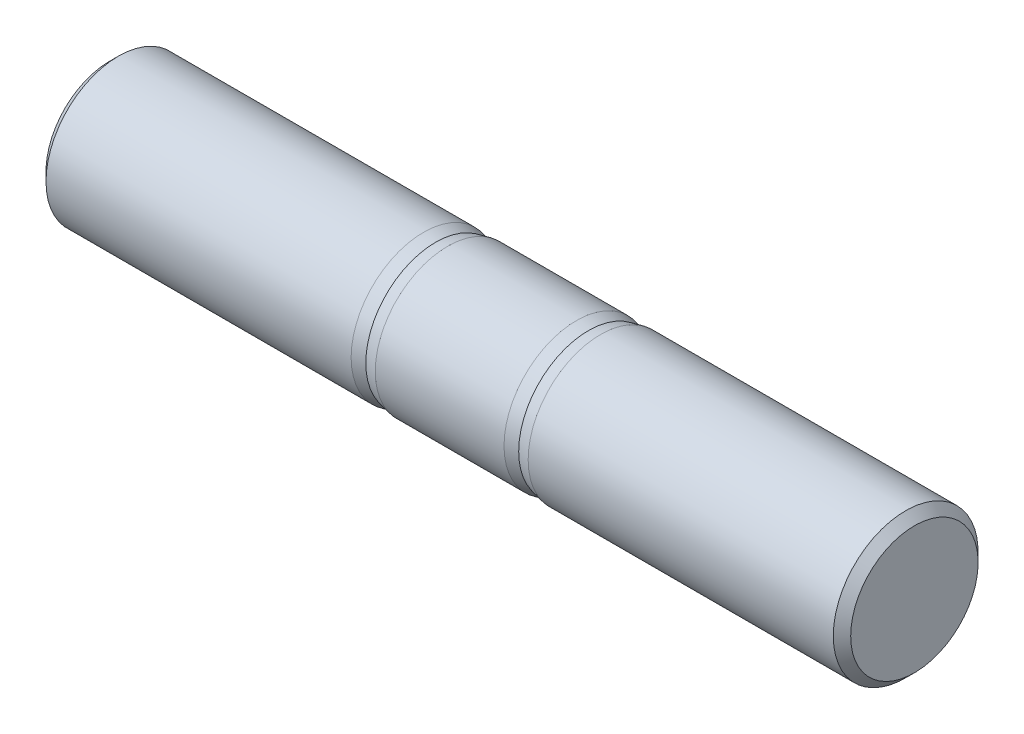
SolidWorks part; units mm, degrees
ref_plane "Front" through (0, 0, 0) normal (0, 0, 1) x (1, 0, 0)
ref_plane "Top" through (0, 0, 0) normal (0, 1, 0) x (1, 0, 0)
ref_plane "Right" through (0, 0, 0) normal (1, 0, 0) x (0, 0, -1)
sketch "Sketch1" plane through (0, 0, 0) normal (0, 0, 1) x (1, 0, 0)
  line L0 (-1.3108, 0) -> (30.3862, 0) construction
  line L1 (0, 0) -> (0, 18)
  line L2 (0, 18) -> (78, 18)
  line L3 (78, 18) -> (84, 16.701)
  line L4 (84, 16.701) -> (116, 16.701)
  line L5 (116, 16.701) -> (122, 18)
  line L6 (122, 18) -> (200, 18)
  line L7 (200, 18) -> (200, 0)
  line L8 (200, 0) -> (0, 0)
  dimension "D2" = 6
  dimension "D1" = 78
  dimension "l" = 200
  dimension "b" = 78
revolve "Base" add sketch "Sketch1" angle 360 about L0
cosmetic thread "ThreadCosmetic1" [suppressed] parameters "D1"=78, "D2"=31.67
cosmetic thread "ThreadCosmetic2" [suppressed] parameters "b"=78, "D2"=31.67
chamfer "HeadChamfer" distance 2.165 angle 45 2 edges at (0, 0, 18) (200, 0, 18)
sketch "Sketch4" plane through (0, 0, 0) normal (0, 0, 1) x (1, 0, 0)
  line L0 (78, 16.701) -> (84, 18)
  line L1 (78, 18) -> (78, -18) construction
  line L2 (84, 18) -> (116, 18)
  line L3 (116, 18) -> (122, 16.701)
  line L4 (122, 18) -> (122, -18) construction
  line L5 (122, 16.701) -> (78, 16.701)
  line L6 (-7.8091, 0) -> (106.8365, 0) construction
  line L8 (84, 33.6577) -> (84, 2.3423) construction
  line L10 (84, 16.701) -> (84, -16.701) construction
  line L11 (84, 16.701) -> (116, 16.701) construction
revolve "BaseBody" add sketch "Sketch4" angle 360 about L6
sketch "Sketch2" plane through (0, 0, 0) normal (0, 0, 1) x (1, 0, 0)
  line L0 (197.835, 16.1251) -> (198.9175, 18)
  line L1 (198.9175, 18) -> (198.9175, 18.5)
  line L2 (198.9175, 18.5) -> (196.7525, 18.5)
  line L3 (196.7525, 18.5) -> (196.7525, 18)
  line L4 (196.7525, 18) -> (197.835, 16.1251)
  line L5 (0, 0) -> (114.8799, 0) construction
  line L6 (197.835, 18) -> (197.835, -18) construction
  dimension "D1" = 60
  dimension "D2" = 60
  dimension "D3" = 0.5
  dimension "D4" = 2.165
  dimension "D5" = 36
revolve "Cut-Revolve10" [suppressed] cut sketch "Sketch2" angle 360 about L5
pattern_linear "LPattern10" [suppressed] count 30 spacing 2.598 along (-1, 0, 0) of bodies 102
sketch "Sketch3" plane through (0, 0, 0) normal (0, 0, 1) x (1, 0, 0)
  line L0 (2.165, 16.1251) -> (3.2475, 18)
  line L1 (3.2475, 18) -> (3.2475, 18.5)
  line L2 (3.2475, 18.5) -> (1.0825, 18.5)
  line L3 (1.0825, 18.5) -> (1.0825, 18)
  line L4 (1.0825, 18) -> (2.165, 16.1251)
  line L5 (0, 0) -> (15.3216, 0) construction
  line L6 (0, 15.835) -> (0, -15.835) construction
  line L7 (2.165, 18) -> (2.165, -18) construction
  dimension "D1" = 60
  dimension "D2" = 60
  dimension "D3" = 36
  dimension "D4" = 0.5
  dimension "D5" = 2.165
revolve "Cut-Revolve11" [suppressed] cut sketch "Sketch3" angle 360 about L5
pattern_linear "LPattern11" [suppressed] count 30 spacing 2.598 along (1, 0, 0) of bodies 104
equation "\"D2@Sketch1\" = \"X@Sketch1\""
equation "\"D2@ThreadCosmetic2\" = \"D2@ThreadCosmetic1\""
equation "\"b@ThreadCosmetic2\" = \"b@Sketch1\""
equation "\"D1@HeadChamfer\" =  ( \"d@Sketch1\" - \"D2@ThreadCosmetic1\" )  / 2"
equation "\"D1@Sketch1\" = \"b@Sketch1\""
equation "\"D5@Sketch2\" = \"d@Sketch1\""
equation "\"D4@Sketch2\" =  ( \"d@Sketch1\" - \"D2@ThreadCosmetic2\" )  / 2"
equation "\"D3@LPattern10\" = \"D4@Sketch2\" * 1.2"
equation "\"D1@LPattern10\" = \"b@ThreadCosmetic2\" / \"D3@LPattern10\""
equation "\"D3@Sketch3\" = \"d@Sketch1\""
equation "\"D5@Sketch3\"  =  ( \"d@Sketch1\" - \"D2@ThreadCosmetic1\" )  / 2"
equation "\"D3@LPattern11\" = \"D5@Sketch3\" * 1.2"
equation "\"D1@LPattern11\" = \"D1@ThreadCosmetic1\" / \"D3@LPattern11\""
equation "\"D1@ThreadCosmetic1\" = \"b@Sketch1\""
